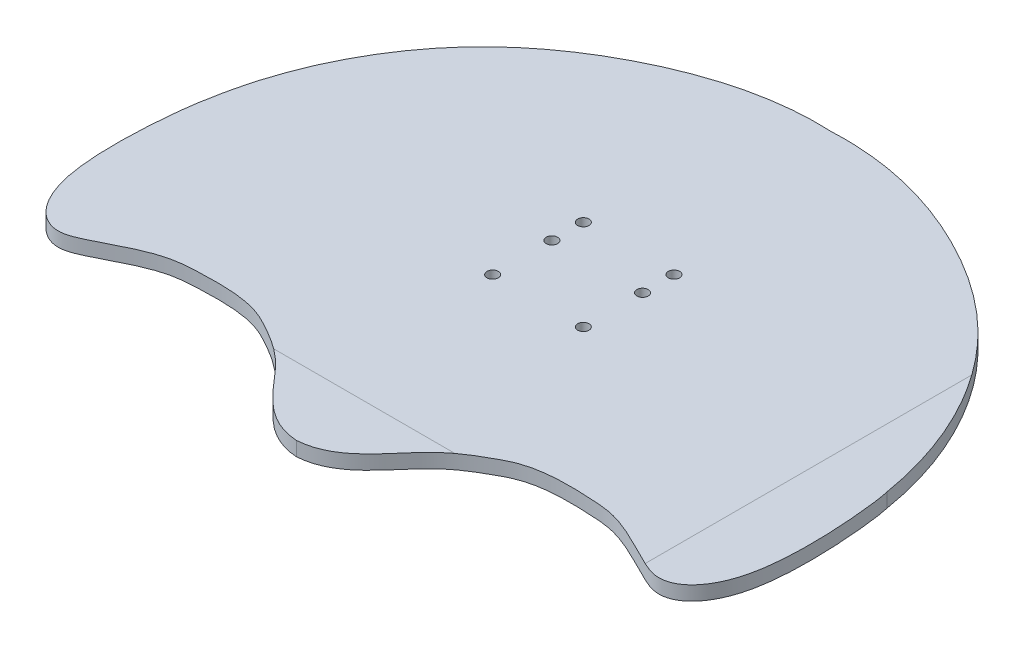
SolidWorks part; units mm, degrees
material "6061-T6 (SS)"
ref_plane "Front Plane" through (0, 0, 0) normal (0, 0, 1) x (1, 0, 0)
ref_plane "Top Plane" through (0, 0, 0) normal (0, 1, 0) x (1, 0, 0)
ref_plane "Right Plane" through (0, 0, 0) normal (1, 0, 0) x (0, 0, -1)
sketch "Sketch3" plane through (0, 0, 0) normal (0, 1, 0) x (1, 0, 0)
  line L0 (0, 0) -> (0, 159.1899) construction
  line L1 (0, 0) -> (0, -140.5301) construction
  line L2 (0, 0) -> (-190.5, 0) construction
  line L3 (0, 0) -> (190.5, 0) construction
  spline S0 degree 3 poles (-190.5, 0) (-184.3927, 37.537) (-157.2613, 93.9641) (-82.3875, 146.6227) (-31.3114, 160.7999) (0, 159.1899) knots 0 0 0 0 0.424401 0.65637 1 1 1 1
  spline S1 degree 3 poles (-190.5, 0) (-192.064, -4.9635) (-201.9672, -83.3146) (-174.6966, -109.29) (-151.6301, -100.568) (-131.4108, -87.7198) (-96.8436, -85.3754) (-78.6925, -86.2588) (-58.8335, -96.8794) (-37.3059, -109.9358) (-21.3496, -139.1148) (0, -140.5301) knots 0 0 0 0 0.166997 0.292321 0.319633 0.426735 0.458914 0.609242 0.64191 0.766802 1 1 1 1
  spline S2 degree 3 poles (190.5, 0) (192.064, -4.9635) (201.9672, -83.3146) (174.6966, -109.29) (151.6301, -100.568) (131.4108, -87.7198) (96.8436, -85.3754) (78.6925, -86.2588) (58.8335, -96.8794) (37.3059, -109.9358) (21.3496, -139.1148) (0, -140.5301) knots 0 0 0 0 0.166997 0.292321 0.319633 0.426735 0.458914 0.609242 0.64191 0.766802 1 1 1 1
  spline S3 degree 3 poles (190.5, 0) (184.3927, 37.537) (157.2613, 93.9641) (82.3875, 146.6227) (31.3114, 160.7999) (0, 159.1899) knots 0 0 0 0 0.424401 0.65637 1 1 1 1
  dimension "D1" = 381
  dimension "D2" = 299.72
  dimension "D3" = 159.1899
  dimension "D4" = 86.8953
  dimension "D5" = 104.4979
  dimension "D6" = 29.1616
  dimension "D7" = 92.2742
  dimension "D8" = 108.411
  dimension "D9" = 67.4883
  dimension "D10" = 43.7314
  dimension "D11" = 117.6915
  dimension "D12" = 162.2568
  dimension "D13" = 89.4522
  dimension "D14" = 140.1036
  dimension "D15" = 175.0666
  dimension "D16" = 50.2669
  dimension "D17" = 101.3666
  dimension "D18" = 138.1225
  dimension "D19" = 155.1557
  dimension "D20" = 192.0074
  dimension "D21" = 193.9268
  dimension "D23" = 76.6666
extrude "Boss-Extrude1" add sketch "Sketch3" along normal blind 7.9502 from surface starting at plane "Top Plane"
sketch "Sketch5" plane through (0, 0, 0) normal (0, -1, 0) x (1, 0, 0)
  line L0 (0, 0) -> (0, -20.32) construction
  line L1 (25.4, -45.72) -> (-25.4, -45.72)
  line L2 (25.4, -45.72) -> (25.4, 5.08)
  line L3 (25.4, 5.08) -> (-25.4, 5.08)
  line L4 (-25.4, -45.72) -> (-25.4, 5.08)
  line L5 (25.4, -45.72) -> (-25.4, 5.08) construction
  line L6 (25.4, 5.08) -> (-25.4, -45.72) construction
  line L7 (-25.4, -45.72) -> (-25.4, -28.0988)
  line L8 (-25.4, -28.0988) -> (25.4, -28.0988) construction
  point P0 (0, -20.32)
  point P3 (0, -20.32)
  dimension "D2" = 50.8
  dimension "D3" = 50.8
  dimension "D4" = 17.6212
hole_wizard "1/4 (0.25) Diameter Hole1" positions "Sketch6" profile "Sketch7" hole size "1/4" standard "ANSI Inch" end condition through all
sketch "Sketch6" plane through (0, 0, 0) normal (0, -1, 0) x (-1, 0, 0)
  point P0 (-25.4, 45.72)
  point P3 (25.4, 45.72)
  point P6 (25.4, -5.08)
  point P9 (-25.4, -5.08)
  point P12 (-25.4, 28.0988)
  point P15 (25.4, 28.0988)
sketch "Sketch7" plane through (25.4, 0, -45.72) normal (1, 0, 0) x (0, 0, -1)
  line L0 (0, 0) -> (0, 7.9502)
  line L1 (0, 7.9502) -> (3.175, 7.9502)
  line L2 (3.175, 7.9502) -> (3.175, 0)
  line L5 (3.175, 0) -> (0, 0)
  line L11 (0, -6.35) -> (0, 107.95) construction
  dimension "Thru Hole Dia." = 6.35
  dimension "Thru Hole Depth" = 7.9502
sketch "Sketch9" plane through (0, 7.9502, 0) normal (0, 1, 0) x (1, 0, 0)
  line L0 (157.5201, -102.5466) -> (157.5201, 80.5195)
  line L1 (-50.7649, -102.4301) -> (50.7649, -102.4301)
  spline S0 degree 3 poles (0, -140.5301) (21.3496, -139.1148) (37.3059, -109.9358) (58.8335, -96.8794) (78.6925, -86.2588) (96.8436, -85.3754) (131.4108, -87.7198) (151.6301, -100.568) (174.6966, -109.29) (201.9672, -83.3146) (192.064, -4.9635) (190.5, 0) knots 0 0 0 0 0.233198 0.35809 0.390758 0.541086 0.573265 0.680367 0.707679 0.833003 1 1 1 1 construction
  spline S1 degree 3 poles (190.5, 0) (184.3927, 37.537) (157.2613, 93.9641) (82.3875, 146.6227) (31.3114, 160.7999) (0, 159.1899) knots 0 0 0 0 0.424401 0.65637 1 1 1 1 construction
  spline S2 degree 3 poles (-190.5, 0) (-192.064, -4.9635) (-201.9672, -83.3146) (-174.6966, -109.29) (-151.6301, -100.568) (-131.4108, -87.7198) (-96.8436, -85.3754) (-78.6925, -86.2588) (-58.8335, -96.8794) (-37.3059, -109.9358) (-21.3496, -139.1148) (0, -140.5301) knots 0 0 0 0 0.166997 0.292321 0.319633 0.426735 0.458914 0.609242 0.64191 0.766802 1 1 1 1 construction
  dimension "D1" = 38.1
split line "Split Line1"
equation "\"Plate thickness\"=0.313"
equation "\"D1@Boss-Extrude1\"=\"Plate thickness\""
equation "\"Bracket Alignment\"= .80"
equation "\"D1@Sketch5\"=\"Bracket Alignment\""
